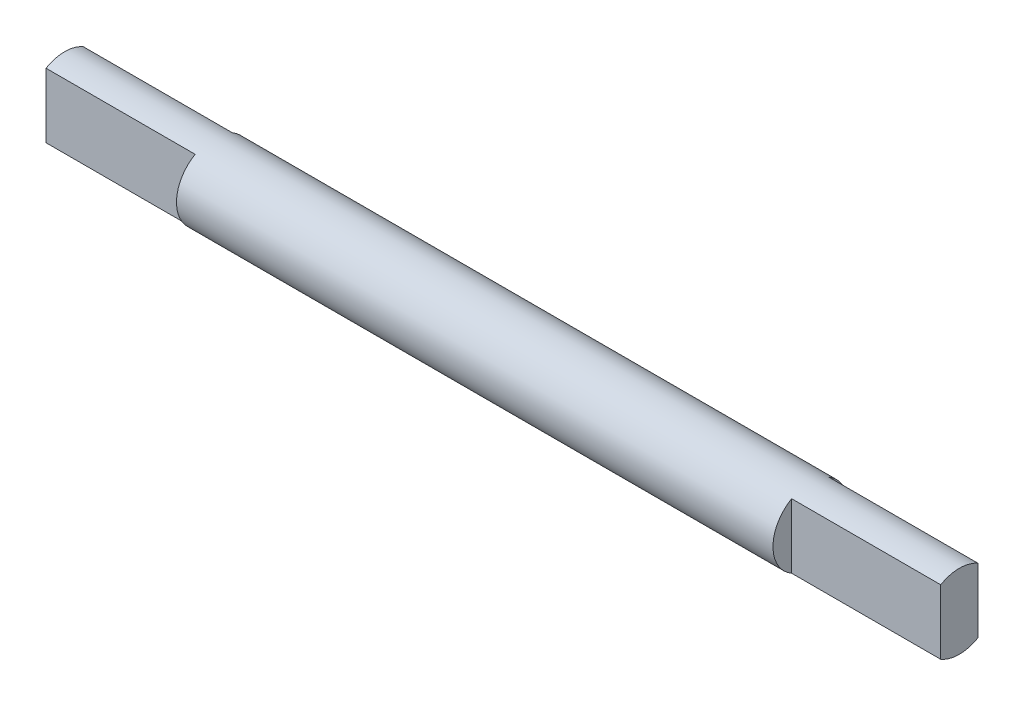
SolidWorks part; units mm, degrees
ref_plane "Front Plane" through (0, 0, 0) normal (0, 0, 1) x (1, 0, 0)
ref_plane "Top Plane" through (0, 0, 0) normal (0, 1, 0) x (1, 0, 0)
ref_plane "Right Plane" through (0, 0, 0) normal (1, 0, 0) x (0, 0, -1)
sketch "Sketch3" plane through (0, 0, 0) normal (1, 0, 0) x (0, 0, -1)
  circle A0 centre (0, 0) radius 12.7
  dimension "D1" = 25.4
extrude "Boss-Extrude1" add sketch "Sketch3" along normal blind 279.4 and the other way blind 25.4
sketch "Sketch4" plane through (0, 0, 0) normal (0, 1, 0) x (1, 0, 0)
  line L0 (-25.4, 12.7) -> (-25.4, -12.7) construction
  line L1 (-25.4, 6.35) -> (25.4, 6.35)
  line L2 (-25.4, 6.35) -> (-25.4, 12.7)
  line L3 (-25.4, 12.7) -> (25.4, 12.7)
  line L4 (25.4, 6.35) -> (25.4, 12.7)
  line L5 (279.4, 12.7) -> (-25.4, 12.7) construction
  line L6 (-25.4, -12.7) -> (279.4, -12.7) construction
  line L7 (-25.4, -6.35) -> (25.4, -6.35)
  line L8 (-25.4, -6.35) -> (-25.4, -12.7)
  line L9 (-25.4, -12.7) -> (25.4, -12.7)
  line L10 (25.4, -6.35) -> (25.4, -12.7)
  dimension "D1" = 50.8
  dimension "D2" = 6.35
extrude "Cut-Extrude1" cut sketch "Sketch4" against normal through all both and the other way through all
sketch "Sketch6" plane through (0, 0, 0) normal (0, 1, 0) x (1, 0, 0)
  line L1 (279.4, -12.7) -> (228.6, -12.7)
  line L2 (279.4, -12.7) -> (279.4, -6.35)
  line L3 (279.4, -6.35) -> (228.6, -6.35)
  line L4 (228.6, -12.7) -> (228.6, -6.35)
  line L5 (279.4, 12.7) -> (228.6, 12.7)
  line L6 (279.4, 12.7) -> (279.4, 6.35)
  line L7 (279.4, 6.35) -> (228.6, 6.35)
  line L8 (228.6, 12.7) -> (228.6, 6.35)
  dimension "D1" = 6.35
  dimension "D2" = 50.8
extrude "Cut-Extrude2" cut sketch "Sketch6" against normal through all both and the other way through all
